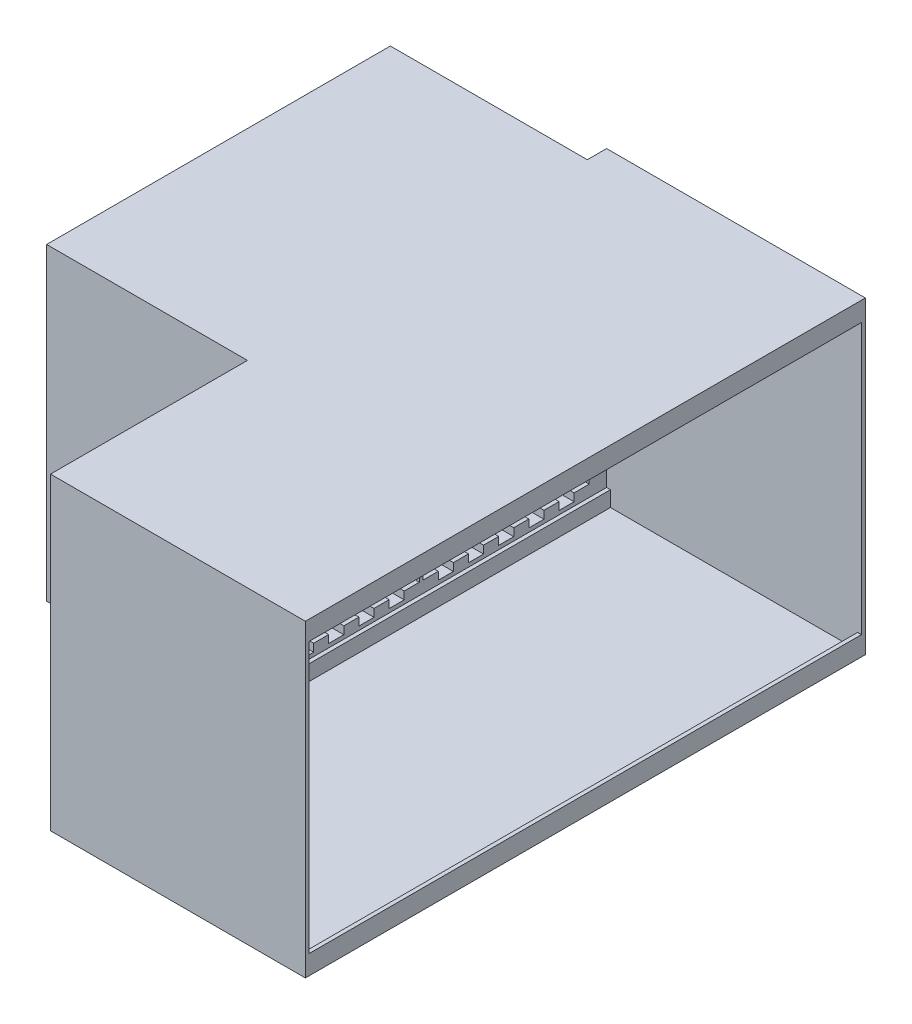
SolidWorks part; units mm, degrees
other "Исправление1"
sketch "Эскиз13" plane through (1050, -360, 1224.5) normal (0.916, -0.3443, 0.206) x (0.3981, 0.8438, -0.36)
ref_plane "Спереди" through (0, 0, 0) normal (0, 0, 1) x (1, 0, 0)
ref_plane "Сверху" through (0, 0, 0) normal (0, 1, 0) x (1, 0, 0)
ref_plane "Справа" through (0, 0, 0) normal (1, 0, 0) x (0, 0, -1)
other "Configuration Table"
sketch "Основа эскиз" plane through (0, 0, 0) normal (1, 0, 0) x (0, 0, -1)
  line L1 (-470, 400) -> (470, 400)
  line L2 (-470, 400) -> (-470, -400)
  line L3 (-470, -400) -> (470, -400)
  line L4 (470, 400) -> (470, -400)
  point P4 (0, 400)
  point P8 (-470, 0)
  dimension "D2" = 940
  dimension "D1" = 800
extrude "Основа" add sketch "Основа эскиз" along normal blind 1180
sketch "Вырез коретки эскиз" plane through (1180, 0, 0) normal (1, 0, 0) x (0, 0, -1)
  line L5 (470, 400) -> (-470, 400) construction
  line L6 (-470, 350) -> (460, 350)
  line L7 (-470, -400) -> (470, -400) construction
  line L8 (-470, 350) -> (-470, -350)
  line L9 (-470, -350) -> (460, -350)
  line L10 (460, 350) -> (460, -350)
  line L11 (-470, 400) -> (-470, -400) construction
  line L12 (470, -400) -> (470, 400) construction
  point P0 (0, 0)
  dimension "D3" = 10
  dimension "D4" = 50
extrude "Вырез коретки" cut sketch "Вырез коретки эскиз" against normal blind 660
sketch "вырез ячейки эскиз" plane through (520, 0, 0) normal (1, 0, 0) x (0, 0, -1)
  line L0 (460, 350) -> (-470, 350) construction
  line L1 (-455, 350) -> (-25, 350)
  line L2 (-455, 350) -> (-455, 30)
  line L3 (-455, 30) -> (-25, 30)
  line L4 (-25, 350) -> (-25, 30)
  line L17 (-470, 350) -> (-470, -350) construction
  dimension "D7" = 430
  dimension "D8" = 320
  dimension "D1" = 15
extrude "вырез ячейки" cut sketch "вырез ячейки эскиз" against normal blind 510
sketch "вырез двери эскиз" plane through (0, 0, 0) normal (-1, 0, 0) x (0, 0, 1)
  line L1 (25, 350) -> (460, 350)
  line L2 (25, 350) -> (25, 30)
  line L3 (25, 30) -> (460, 30)
  line L4 (460, 350) -> (460, 30)
  line L6 (455, 30) -> (25, 30) construction
  line L7 (25, 30) -> (25, 350) construction
  line L8 (455, 350) -> (455, 30) construction
  line L9 (455, 350) -> (455, 30) construction
  line L10 (25, 350) -> (455, 350) construction
  dimension "D2" = 5
extrude "вырез двери" cut sketch "вырез двери эскиз" against normal blind 10
sketch "Вырез основание низ эскиз" plane through (0, -350, 0) normal (0, 1, 0) x (1, 0, 0)
  line L0 (1180, -470) -> (1180, 460) construction
  line L1 (530, 460) -> (1170, 460)
  line L2 (530, 460) -> (530, -470)
  line L3 (530, -470) -> (1170, -470)
  line L4 (1170, 460) -> (1170, -470)
  line L5 (520, 460) -> (1180, 460) construction
  line L6 (520, -470) -> (1180, -470) construction
  dimension "D1" = 10
  dimension "D2" = 640
extrude "Вырез основание низ" cut sketch "Вырез основание низ эскиз" against normal blind 40
sketch "Вырез основания верх эскиз" plane through (0, 350, 0) normal (0, -1, 0) x (1, 0, 0)
  line L0 (520, 470) -> (1180, 470) construction
  line L1 (530, -460) -> (1170, -460)
  line L2 (530, -460) -> (530, 470)
  line L3 (530, 470) -> (1170, 470)
  line L4 (1170, -460) -> (1170, 470)
  line L5 (520, -460) -> (1180, -460) construction
  line L6 (1180, -460) -> (1180, 470) construction
  dimension "D1" = 10
  dimension "D2" = 640
extrude "Вырез основание верх" cut sketch "Вырез основания верх эскиз" against normal blind 40
sketch "вырез полозья эскиз" plane through (520, 0, 0) normal (1, 0, 0) x (0, 0, -1)
  line L0 (-455, 30) -> (-25, 30) construction
  line L1 (-415.9091, 30) -> (-376.8182, 30)
  line L2 (-415.9091, 30) -> (-415.9091, 10)
  line L3 (-415.9091, 10) -> (-376.8182, 10)
  line L4 (-376.8182, 30) -> (-376.8182, 10)
  dimension "D2" = 39.0909
  dimension "D3" = 39.0909
extrude "Вырез полозья" cut sketch "вырез полозья эскиз" against normal blind 510
pattern_linear "Линейный массив полозьев" count 5 spacing 78.1818 along (0, 0, -1) of "Вырез полозья"
pattern_linear "Линейный массив ячеек" count 2 spacing 440 along (0, 0, -1) count 2 spacing 350 along (0, -1, 0) of "Линейный массив полозьев", "вырез двери", "вырез ячейки"
sketch "Основание эскиз" plane through (0, 0, 470) normal (0, 0, 1) x (1, 0, 0)
  line L0 (1180, -400) -> (1180, -350)
  line L1 (1180, -350) -> (1170, -350)
  line L2 (1170, -350) -> (1170, -390)
  line L3 (1170, -390) -> (530, -390)
  line L4 (530, -390) -> (530, -350)
  line L5 (530, -350) -> (520, -350)
  line L6 (520, -350) -> (520, -400)
  line L7 (1180, -400) -> (0, -400) construction
  line L8 (520, -400) -> (1180, -400)
  line L9 (1170, 350) -> (1180, 350)
  line L10 (1180, 350) -> (1180, 400)
  line L11 (1180, 400) -> (520, 400)
  line L12 (1180, 400) -> (0, 400) construction
  line L13 (520, 400) -> (520, 350)
  line L14 (520, 350) -> (530, 350)
  line L15 (530, 350) -> (530, 390)
  line L16 (530, 390) -> (1170, 390)
  line L17 (1170, 390) -> (1170, 350)
extrude "Основание" add sketch "Основание эскиз" along normal blind 500
sketch "Стенка боквая эскиз" plane through (0, 0, 970) normal (0, 0, 1) x (1, 0, 0)
  line L1 (1180, 400) -> (520, 400)
  line L2 (1180, 400) -> (1180, -400)
  line L3 (1180, -400) -> (520, -400)
  line L4 (520, 400) -> (520, -400)
extrude "Стенка боковая" add sketch "Стенка боквая эскиз" along normal blind 10
sketch "Эскиз14" plane through (0, 0, -470) normal (0, 0, -1) x (-1, 0, 0)
  line L0 (-1180, 400) -> (0, 400) construction
  line L1 (0, -400) -> (-510, -400)
  line L2 (0, -400) -> (0, 400)
  line L3 (0, 400) -> (-510, 400)
  line L4 (-510, -400) -> (-510, 400)
  dimension "D1" = 510
extrude "Вырез-Вытянуть1" cut sketch "Эскиз14" against normal blind 50
equation "\"Ширина груза\"= 420"
equation "\"Глубина груза\"= 490"
equation "\"Высота груза\"= 297"
equation "\"Ширина ячейки\"= \"Ширина груза\" + 10"
equation "\"Глубина ячейки\"= \"Глубина груза\" + 10"
equation "\"Высота ячейки\"= \"Высота груза\" + 10 + 13"
equation "\"Колво ячеек ширина\"= 2"
equation "\"Колво ячеек высота\"= 2"
equation "\"Толщина стенки\"= 10"
equation "\"D2@Основа эскиз\"=( \"Ширина ячейки\" + \"Толщина стенки\" + \"Крепление дверцы\" ) * \"Колво ячеек ширина\" + \"Ширина пластины\""
equation "\"D1@Основа эскиз\" = ( \"Высота ячейки\" + \"Толщина стенки\" + \"Высота пола\" ) * \"Колво ячеек высота\" + \"Отступ рейки\" * 2 + \"Высота рейки\" * 2 + \"Толщина стенки\" * 2"
equation "\"Крепление дверцы\"= 5"
equation "\"D7@вырез ячейки эскиз\"= \"Ширина ячейки\""
equation "\"D1@вырез ячейки эскиз\" = \"Толщина стенки\" + \"Крепление дверцы\""
equation "\"D8@вырез ячейки эскиз\"= \"Высота ячейки\""
equation "\"D2@вырез двери эскиз\"= \"Крепление дверцы\""
equation "\"D1@Основа\" = \"Глубина ячейки\" + \"Глубина каретки\" + \"Толщина стенки\" * 4 + \"Ширина рейки\" * 2"
equation "\"D1@Вырез коретки\"= \"Глубина каретки\" + \"Толщина стенки\" * 2 + \"Ширина рейки\" * 2"
equation "\"D1@Вырез основание низ эскиз\"=\"Толщина стенки\" "
equation "\"Ширина рейки\"= \"Толщина шестерни\""
equation "\"D1@вырез ячейки\"= \"Глубина ячейки\" + \"Толщина стенки\""
equation "\"D1@вырез двери\"= \"Толщина стенки\""
equation "\"D2@Вырез основание низ эскиз\"=\"Глубина каретки\" + \"Ширина рейки\" * 2"
equation "\"Высота рейки\"= 20"
equation "\"D1@Вырез основания верх эскиз\"=\"Толщина стенки\""
equation "\"D2@Вырез основания верх эскиз\"=\"Глубина каретки\" + \"Ширина рейки\" * 2"
equation "\"D1@Вырез основание верх\" = \"Высота рейки\" + \"Отступ рейки\""
equation "\"D4@Вырез коретки эскиз\"=\"Толщина стенки\"  + \"Высота рейки\" + \"Отступ рейки\""
equation "\"D1@Вырез коретки эскиз\"=\"Толщина стенки\" + \"Высота рейки\" + \"Отступ рейки\" "
equation "\"D3@Вырез коретки эскиз\" = \"Толщина стенки\""
equation "\"D1@Вырез основание низ\" = \"Высота рейки\" + \"Отступ рейки\""
equation "\"Высота пола\"= 20"
equation "\"Колво полозьев\"= 5"
equation "\"D1@вырез полозья эскиз\" = \"Высота пола\""
equation "\"D2@вырез полозья эскиз\" = \"Ширина ячейки\" /  ( \"Колво полозьев\" * 2 + 1 ) "
equation "\"D3@вырез полозья эскиз\"= \"Ширина ячейки\" / ( \"Колво полозьев\" * 2 + 1 )"
equation "\"D1@Вырез полозья\" = \"Глубина ячейки\" + \"Толщина стенки\""
equation "\"D1@Линейный массив полозьев\" = \"Колво полозьев\""
equation "\"D3@Линейный массив полозьев\" = \"Ширина ячейки\" /  ( \"Колво полозьев\" * 2 + 1 )  * 2"
equation "\"D1@Линейный массив ячеек\" = \"Колво ячеек ширина\""
equation "\"D2@Линейный массив ячеек\" = \"Колво ячеек высота\""
equation "\"D3@Линейный массив ячеек\" = \"Ширина ячейки\" + \"Толщина стенки\""
equation "\"D4@Линейный массив ячеек\" = \"Высота ячейки\" + \"Высота пола\" + \"Толщина стенки\""
equation "\"Отступ рейки\"= 20"
equation "\"Глубина каретки\"= \"Глубина ячейки\" + 80"
equation "\"D1@Стенка боковая\" = \"Толщина стенки\""
equation "\"Длинна рейки\"= ( \"Ширина ячейки\" + \"Толщина стенки\" + \"Крепление дверцы\" ) * \"Колво ячеек ширина\" + \"Ширина ячейки выгрузки\" * \"Колво выгрузки\" + \"Толщина стенки\""
equation "\"D1@Основание\" = \"Длинна рейки\" -  ( \"Ширина ячейки\" + \"Толщина стенки\" + \"Крепление дверцы\" )  * \"Колво ячеек ширина\" - \"Толщина стенки\""
equation "\"Отступ шпильки\"= 20"
equation "\"Диаметр шпильки\"= 5"
equation "\"Длинна шпильки\"= ( \"Высота ячейки\" + \"Толщина стенки\" + \"Высота пола\" ) * \"Колво ячеек высота\" + ( \"Толщина стенки\" + \"Отступ рейки\" ) * 2"
equation "\"Ширина пластины\"= 50  "
equation "\"Высота зона выгрузки\"= \"Высота ячейки\" * 2 + \"Толщина стенки\" * 2"
equation "\"Колво выгрузки\"= 1"
equation "\"D1@Эскиз14\"= \"Толщина стенки\" + \"Глубина ячейки\""
equation "\"D1@Вырез-Вытянуть1\"= \"Ширина пластины\""
equation "\"Ширина ячейки выгрузки\"= \"Ширина ячейки\" + \"Толщина стенки\" + \"Отступ крепления мотора фиксации\"*2"
equation "\"Отступ крепления мотора фиксации\" = 30"
